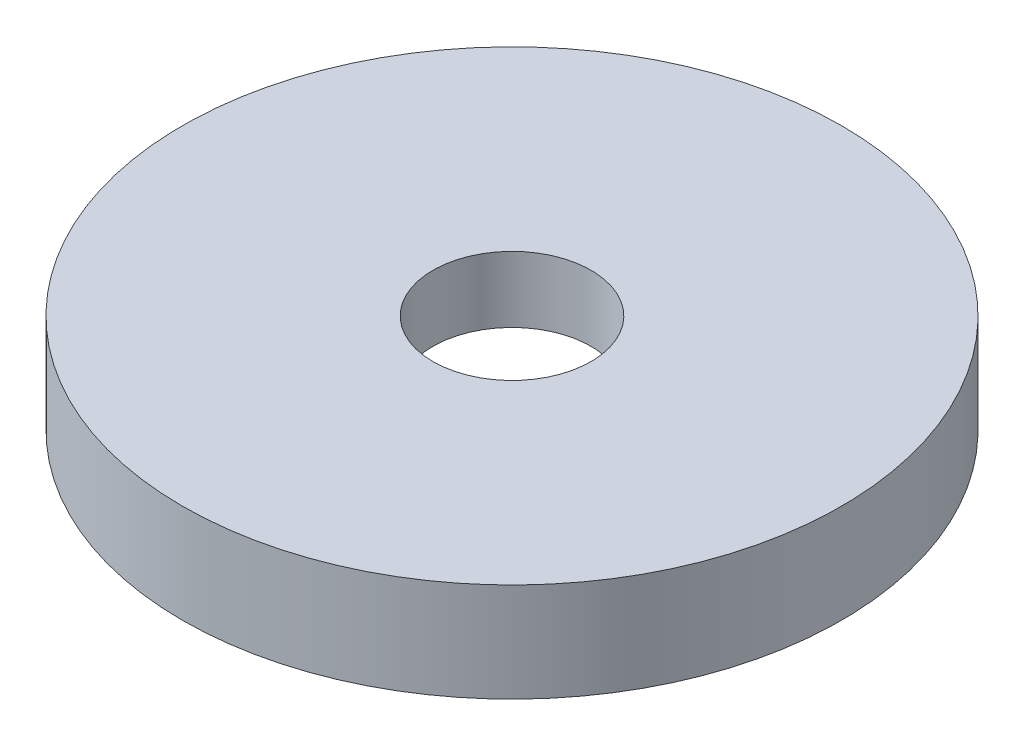
SolidWorks part; units mm, degrees
ref_plane "Front Plane" through (0, 0, 0) normal (0, 0, 1) x (1, 0, 0)
ref_plane "Top Plane" through (0, 0, 0) normal (0, 1, 0) x (1, 0, 0)
ref_plane "Right Plane" through (0, 0, 0) normal (1, 0, 0) x (0, 0, -1)
sketch "Sketch1" plane through (0, 0, 0) normal (0, 1, 0) x (1, 0, 0)
  circle A0 centre (0, 0) radius 5
  circle A1 centre (0, 0) radius 1.2
  circle A2 centre (0, 0) radius 2.5
  dimension "D1" = 10
  dimension "D2" = 2.4
  dimension "D3" = 5
extrude "Boss-Extrude1" add sketch "Sketch1" along normal blind 1.5 contours A0 A2 | A2 A1 region at (-4.8586, 0, 0) region at (-2.4293, 0, 0)
extrude "Cut-Extrude1" cut sketch "Sketch1<3>" along normal blind 0.5 contours A2 A1 region at (-2.4293, 0, 0)
sketch "Sketch1<3>" plane through (0, 0, 0) normal (0, 1, 0) x (1, 0, 0) same geometry as "Sketch1"
